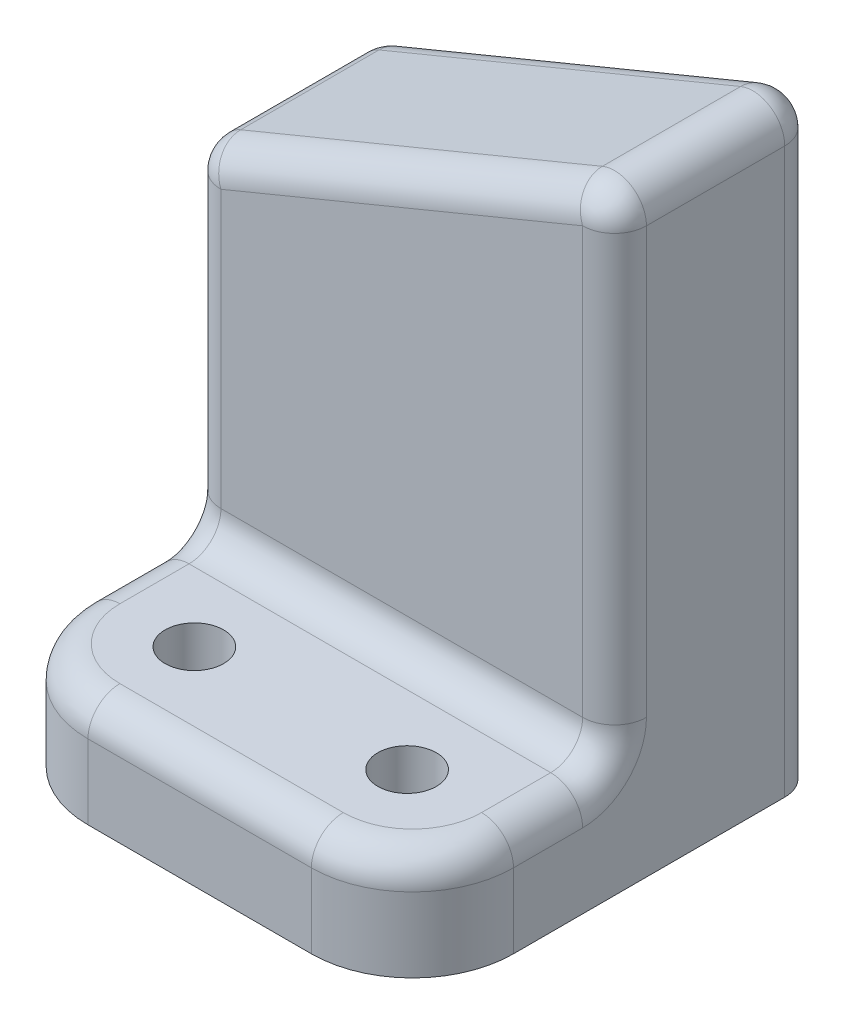
SolidWorks part; units mm, degrees
other "Leg Flip Up Support"
ref_plane "Front Plane" through (0, 0, 0) normal (0, 0, 1) x (1, 0, 0)
ref_plane "Top Plane" through (0, 0, 0) normal (0, 1, 0) x (1, 0, 0)
ref_plane "Right Plane" through (0, 0, 0) normal (1, 0, 0) x (0, 0, -1)
sketch "Profile Sketch" plane through (0, 0, 0) normal (1, 0, 0) x (0, 0, -1)
  line L0 (0, 0) -> (0, 60)
  line L1 (0, 60) -> (-19, 60)
  line L2 (-19, 60) -> (-19, 10)
  line L3 (-19, 10) -> (-38, 10)
  line L4 (-38, 10) -> (-38, 0)
  line L5 (-38, 0) -> (0, 0)
  dimension "D1" = 10
  dimension "D2" = 19
  dimension "D3" = 60
  dimension "D4" = 38
extrude "Profile Extrude" add sketch "Profile Sketch" along normal mid plane 40
sketch "Top Angle Cut Sketch" plane through (0, 0, 0) normal (0, 0, -1) x (-1, 0, 0)
  line L0 (-25.5131, 59.7741) -> (36.4785, 34.2026)
  line L1 (-20, 0) -> (-20, 60) construction
  line L2 (20, 0) -> (20, 60) construction
  line L3 (-20, 0) -> (20, 0) construction
  line L4 (-25.5131, 59.7741) -> (-25.5131, 65.5292)
  line L5 (-25.5131, 65.5292) -> (36.4785, 65.5292)
  line L6 (36.4785, 65.5292) -> (36.4785, 34.2026)
  circle A0 centre (-17, 53.0173) radius 3 construction
  circle A1 centre (17, 38.9923) radius 3 construction
  dimension "D3" = 6
  dimension "D1" = 38.9923
  dimension "D2" = 53.0173
extrude "Top Angle Cut" cut sketch "Top Angle Cut Sketch" against normal up to next
fillet "Base Fillet" radius 9.5 2 edges at (-20, 5, 38) (20, 5, 38)
fillet "Top Edges Fillets" radius 3 3 edges at (0, 10, 19) (20, 57.5, 9.5) (-20, 41, 9.5)
fillet "Corner Fillets" radius 3 17 edges at (18.6685, 55.5105, 19) (-1.144, 48.7781, 19) (-19.4932, 40.6608, 19) (-20, 25.9961, 19) (-20, 10.8787, 19.8787) (-20, 10, 25.25) (-17.2175, 10, 35.2175) (0, 10, 38) (17.2175, 10, 35.2175) (20, 10, 25.25) (20, 10.8787, 19.8787) (-20, 19.4961, 0) (-19.4932, 40.6608, 0) (-1.144, 48.7781, 0) (18.6685, 55.5105, 0) (20, 33.0086, 19) (20, 26.5086, 0)
sketch "Hole Position Sketch" plane through (0, 10, 0) normal (0, 1, 0) x (1, 0, 0)
  line L0 (0, -38) -> (0, 0) construction
  line L1 (10.5, -38) -> (-10.5, -38) construction
  point P0 (-10, -28.5)
  point P1 (10, -28.5)
  dimension "D1" = 9.5
  dimension "D2" = 20
hole_wizard "Mounting Holes" positions "Mounting Holes Position Sketch" profile "Mounting Holes Profile Sketch" hole size "M5" standard "ANSI Metric" end condition up to next
sketch3d "Mounting Holes Position Sketch"
  point P0 (-10, 10, 28.5)
  point P3 (10, 10, 28.5)
sketch "Mounting Holes Profile Sketch" plane through (-10, 10, 28.5) normal (1, 0, 0) x (0, 0, 1)
  line L0 (0, 0) -> (0, 10)
  line L1 (0, 10) -> (2.75, 10)
  line L2 (2.75, 10) -> (2.75, 0)
  line L5 (2.75, 0) -> (0, 0)
  line L11 (0, -6.35) -> (0, 107.95) construction
  dimension "Thru Hole Dia." = 5.5
  dimension "Thru Hole Depth" = 10
